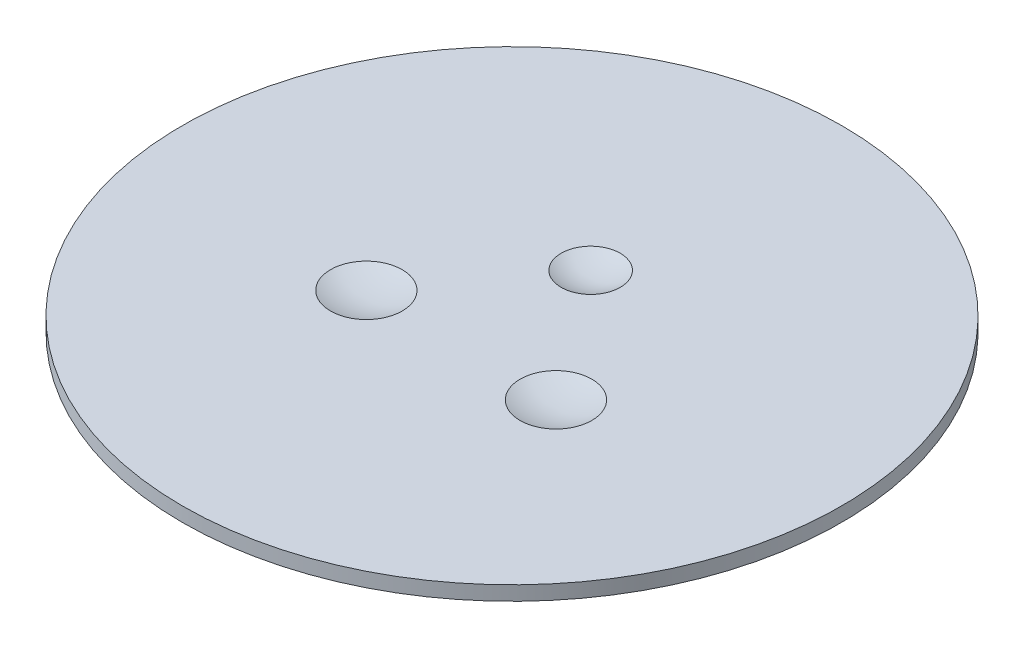
SolidWorks part; units mm, degrees
ref_plane "Front Plane" through (0, 0, 0) normal (0, 0, 1) x (1, 0, 0)
ref_plane "Top Plane" through (0, 0, 0) normal (0, 1, 0) x (1, 0, 0)
ref_plane "Right Plane" through (0, 0, 0) normal (1, 0, 0) x (0, 0, -1)
sketch "Sketch1" plane through (0, 0, 0) normal (0, 1, 0) x (1, 0, 0)
  line L0 (-330.835, -177.3911) -> (0, 0) construction
  line L1 (-330.835, -177.3911) -> (330.835, -177.3911) construction
  line L2 (330.835, -177.3911) -> (0, 274.5232) construction
  line L3 (0, 274.5232) -> (-330.835, -177.3911) construction
  line L4 (0, 0) -> (330.835, -177.3911) construction
  circle A1 centre (0, 0) radius 1150
  point P8 (0, 0)
  dimension "D1" = 2300
  dimension "D2" = 661.67
  dimension "D3" = 560.07
  dimension "D4" = 560.07
  dimension "D5" = 177.3911
extrude "Boss-Extrude1" add sketch "Sketch1" along normal blind 50
ref_plane "Plane1" through (0, 0, 177.3911) normal (0, 0, 1) x (1, 0, 0)
sketch "Sketch3" plane through (0, 0, 177.3911) normal (0, 0, 1) x (1, 0, 0)
  line L0 (1150, 50) -> (-1150, 50) construction
  line L2 (457.5865, 50) -> (455.8977, 50)
  line L3 (-457.5865, 50) -> (-457.5865, 50.6966)
  line L4 (0, -1265) -> (0, 1265) construction
  line L5 (-205.7723, 50) -> (-330.835, 50)
  line L6 (457.5865, 50) -> (457.5865, 50.6966)
  line L7 (-330.835, 25.4) -> (-330.835, 50)
  line L8 (-455.8977, 50) -> (-457.5865, 50)
  line L9 (330.835, 50) -> (330.835, 25.4)
  line L10 (330.835, 50) -> (205.7723, 50)
  arc A0 (-457.5865, 50.6966) -> (-455.8977, 50) centre (-330.835, 355.6) ccw
  arc A1 (457.5865, 50.6966) -> (455.8977, 50) centre (330.835, 355.6) cw
  arc A2 (-330.835, 25.4) -> (-205.7723, 50) centre (-330.835, 355.6) ccw
  arc A3 (330.835, 25.4) -> (205.7723, 50) centre (330.835, 355.6) cw
  point P0 (330.835, 0)
  point P2 (-330.835, 0)
  dimension "D1" = 660.4
  dimension "D2" = 355.6
revolve "Cut-Revolve2" cut sketch "Sketch3" angle 360 about L7 region at (-283.6944, 40.1279, 177.3911)
revolve "Cut-Revolve3" cut sketch "Sketch3<4>" angle 360 about L9
sketch "Sketch3<4>" plane through (0, 0, 177.3911) normal (0, 0, 1) x (1, 0, 0) same geometry as "Sketch3"
ref_plane "Plane2" through (0, 0, -274.5232) normal (0, 0, 1) x (1, 0, 0)
sketch "Sketch6" plane through (0, 0, -274.5232) normal (0, 0, 1) x (1, 0, 0)
  line L0 (1150, 50) -> (-1150, 50) construction
  line L1 (103.1599, 50) -> (0, 50)
  line L2 (0, 25.4) -> (0, 50)
  arc A0 (0, 25.4) -> (103.1599, 50) centre (0, 254) ccw
  point P0 (0, 0)
  point P5 (0, 0)
  point P6 (0, 25.4)
  dimension "D1" = 457.2
revolve "Cut-Revolve4" cut sketch "Sketch6" angle 360 about L2 region at (38.9785, 40.1132, -274.5232)
ref_plane "Plane3" through (0, 50.6966, 0) normal (0, 1, 0) x (1, 0, 0)
